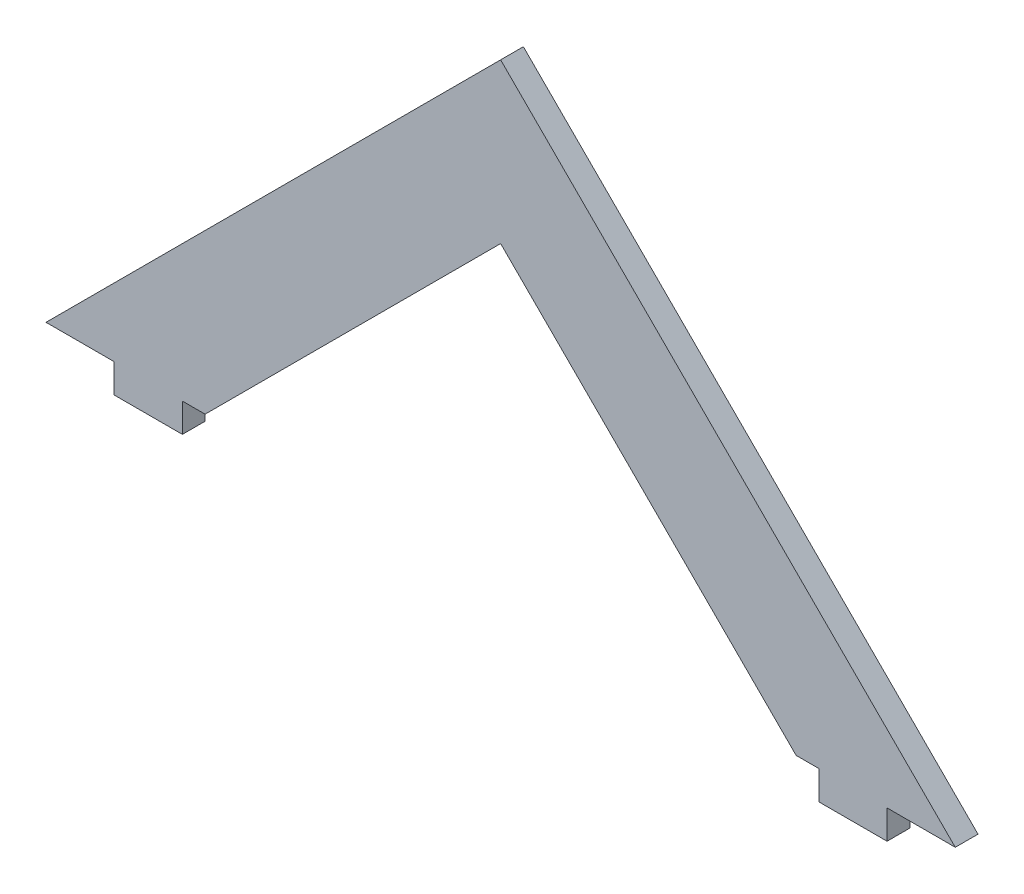
SolidWorks part; units mm, degrees
ref_plane "Front Plane" through (0, 0, 0) normal (0, 0, 1) x (1, 0, 0)
ref_plane "Top Plane" through (0, 0, 0) normal (0, 1, 0) x (1, 0, 0)
ref_plane "Right Plane" through (0, 0, 0) normal (1, 0, 0) x (0, 0, -1)
sketch "Sketch1" plane through (0, 0, 0) normal (0, 0, 1) x (1, 0, 0)
  line L0 (30, 0) -> (15, 0)
  line L1 (15, 0) -> (15, 6.35)
  line L2 (15, 6.35) -> (0, 6.35)
  line L3 (0, 6.35) -> (100, 106.35)
  line L4 (100, 106.35) -> (200, 6.35)
  line L5 (200, 6.35) -> (185, 6.35)
  line L6 (185, 6.35) -> (185, 0)
  line L7 (185, 0) -> (170, 0)
  line L8 (170, 0) -> (170, 6.35)
  line L9 (170, 6.35) -> (165, 6.35)
  line L10 (165, 6.35) -> (100, 71.35)
  line L11 (100, 71.35) -> (35, 6.35)
  line L12 (35, 6.35) -> (30, 6.35)
  line L13 (30, 6.35) -> (30, 0)
  point P20 (103.6937, 115.4537)
  point P24 (0, 0)
  point P26 (107.1636, 70.954)
  dimension "D1" = 5
  dimension "D2" = 5
extrude "Boss-Extrude1" add sketch "Sketch1" along normal blind 5
